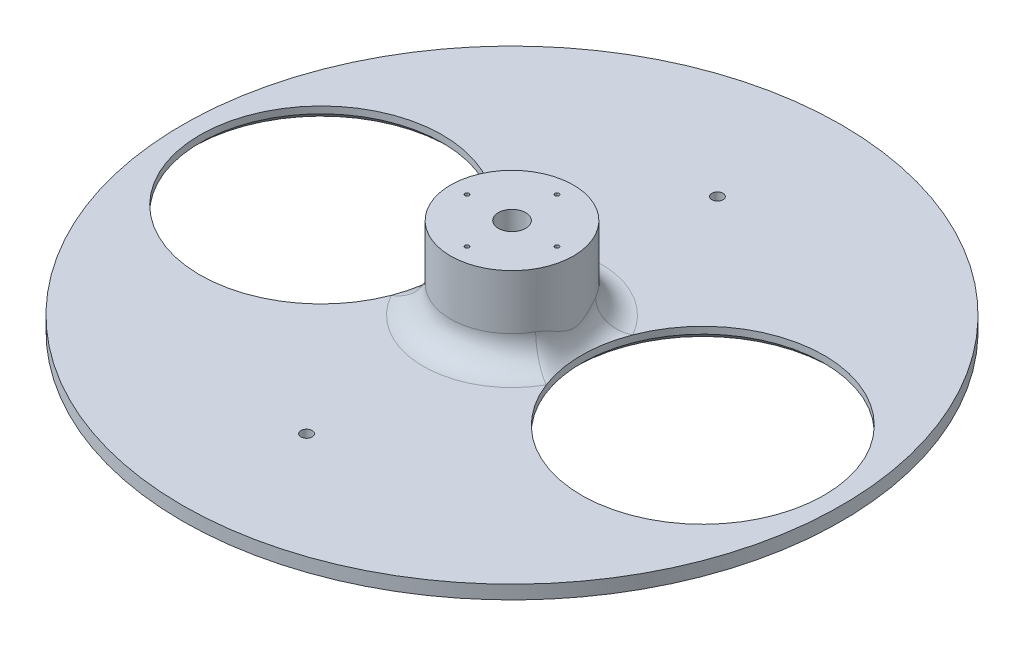
SolidWorks part; units mm, degrees
ref_plane "Front Plane" through (0, 0, 0) normal (0, 0, 1) x (1, 0, 0)
ref_plane "Top Plane" through (0, 0, 0) normal (0, 1, 0) x (1, 0, 0)
ref_plane "Right Plane" through (0, 0, 0) normal (1, 0, 0) x (0, 0, -1)
sketch "Sketch1" plane through (0, 0, 0) normal (0, 1, 0) x (1, 0, 0)
  circle A0 centre (0, 0) radius 120.65
  dimension "D1" = 241.3
extrude "Boss-Extrude1" add sketch "Sketch1" along normal blind 5
sketch "Sketch6" plane through (0, 5, 0) normal (0, 1, 0) x (1, 0, 0)
  circle A0 centre (0, 0) radius 22.5
  dimension "D1" = 45
extrude "Boss-Extrude2" add sketch "Sketch6" along normal blind 30
sketch "Sketch2" plane through (0, 35, 0) normal (0, 1, 0) x (1, 0, 0)
  circle A1 centre (0, 0) radius 16.5 construction
  circle A3 centre (16.5, 0) radius 0.75
  circle A5 centre (0, -16.5) radius 0.75
  circle A7 centre (-16.5, 0) radius 0.75
  circle A9 centre (0, 16.5) radius 0.75
  point P23 (0, 0)
  dimension "D2" = 33
  dimension "D3" = 1.5
  dimension "D5" = 4
extrude "Cut-Extrude1" cut sketch "Sketch2" against normal blind 15
sketch "Sketch3" plane through (0, 0, 0) normal (0, -1, 0) x (1, 0, 0)
  circle A0 centre (0, 0) radius 69.85 construction
  circle A1 centre (69.85, 0) radius 44.4
  circle A2 centre (-69.85, 0) radius 44.4
  point P9 (0, 0)
  dimension "D1" = 139.7
  dimension "D2" = 88.8
  dimension "D3" = 2
extrude "Cut-Extrude2" cut sketch "Sketch3" against normal through all
chamfer "Chamfer1" distance 2.5 angle 45 2 edges at (69.85, 0, -44.4) (-69.85, 0, -44.4)
sketch "Sketch4" plane through (0, 0, 0) normal (0, -1, 0) x (1, 0, 0)
  circle A0 centre (0, 0) radius 5
  dimension "D1" = 10
sketch "Sketch5" plane through (0, 5, 0) normal (0, 1, 0) x (1, 0, 0)
  line L0 (0, 0) -> (27.95, 0) construction
  circle A0 centre (0, 75.21) radius 2.05
  circle A1 centre (69.85, 0) radius 41.9 construction
  circle A2 centre (0, -75.21) radius 2.05
  point P12 (0, 75.21)
  dimension "D1" = 4.1
  dimension "D2" = 75.21
extrude "Cut-Extrude3" cut sketch "Sketch5" against normal through all
extrude "Cut-Extrude4" cut sketch "Sketch4" against normal through all both and the other way through all
fillet "Fillet1" radius 10 1 edges at (0, 5, 22.5)
